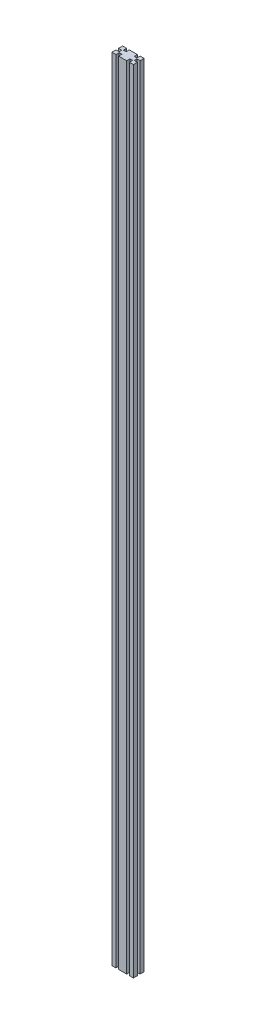
SolidWorks part; units mm, degrees
ref_plane "Front Plane" through (0, 0, 0) normal (0, 0, 1) x (1, 0, 0)
ref_plane "Top Plane" through (0, 0, 0) normal (0, 1, 0) x (1, 0, 0)
ref_plane "Right Plane" through (0, 0, 0) normal (1, 0, 0) x (0, 0, -1)
sketch "Sketch1" plane through (0, 0, 0) normal (0, 1, 0) x (1, 0, 0)
  line L1 (-20, -10) -> (20, -10)
  line L2 (-20, -10) -> (-20, 10)
  line L3 (-20, 10) -> (20, 10)
  line L4 (20, -10) -> (20, 10)
  line L5 (-20, -10) -> (20, 10) construction
  line L6 (-20, 10) -> (20, -10) construction
  point P0 (0, 0)
  dimension "D1" = 20
  dimension "D2" = 40
extrude "Boss-Extrude1" add sketch "Sketch1" along normal blind 736.6 and the other way blind 736.6
sketch "Sketch2" plane through (0, 0, 0) normal (0, 1, 0) x (1, 0, 0)
  line L0 (-20, 10) -> (0, 10) construction
  line L1 (20, 10) -> (-20, 10) construction
  line L2 (0, 10) -> (20, 10) construction
  line L4 (-20, 10) -> (-20, -10) construction
  line L5 (-12.5, 4) -> (-7.5, 4)
  line L6 (-12.5, 4) -> (-12.5, 16)
  line L7 (-12.5, 16) -> (-7.5, 16)
  line L8 (-7.5, 4) -> (-7.5, 16)
  line L9 (-12.5, 4) -> (-7.5, 16) construction
  line L10 (-12.5, 16) -> (-7.5, 4) construction
  line L11 (-14, 2.5) -> (-26, 2.5)
  line L12 (-14, 2.5) -> (-14, -2.5)
  line L13 (-14, -2.5) -> (-26, -2.5)
  line L14 (-26, 2.5) -> (-26, -2.5)
  line L15 (-14, 2.5) -> (-26, -2.5) construction
  line L16 (-14, -2.5) -> (-26, 2.5) construction
  line L17 (-55, 0) -> (55, 0) construction
  line L18 (-14, 2.5) -> (-26, -2.5) construction
  line L19 (-14, -2.5) -> (-26, 2.5) construction
  line L20 (-12.5, -16) -> (-7.5, -4) construction
  line L21 (-12.5, -4) -> (-7.5, -16) construction
  line L22 (-14, 2.5) -> (-26, 2.5)
  line L23 (-14, -2.5) -> (-26, -2.5)
  line L24 (-7.5, -4) -> (-7.5, -16)
  line L25 (-12.5, -16) -> (-7.5, -16)
  line L26 (-12.5, -4) -> (-12.5, -16)
  line L27 (-12.5, -4) -> (-7.5, -4)
  line L28 (0, -55) -> (0, 55) construction
  line L29 (12.5, -4) -> (7.5, -16) construction
  line L30 (12.5, -16) -> (7.5, -4) construction
  line L31 (14, -2.5) -> (26, 2.5) construction
  line L32 (14, 2.5) -> (26, -2.5) construction
  line L33 (14, -2.5) -> (26, 2.5) construction
  line L34 (14, 2.5) -> (26, -2.5) construction
  line L35 (12.5, 16) -> (7.5, 4) construction
  line L36 (12.5, 4) -> (7.5, 16) construction
  line L37 (20, 10) -> (0, 10) construction
  line L38 (12.5, -4) -> (7.5, -4)
  line L39 (12.5, -4) -> (12.5, -16)
  line L40 (12.5, -16) -> (7.5, -16)
  line L41 (7.5, -4) -> (7.5, -16)
  line L42 (14, -2.5) -> (26, -2.5)
  line L43 (14, 2.5) -> (26, 2.5)
  line L44 (26, 2.5) -> (26, -2.5)
  line L45 (14, -2.5) -> (26, -2.5)
  line L46 (14, 2.5) -> (14, -2.5)
  line L47 (14, 2.5) -> (26, 2.5)
  line L48 (7.5, 4) -> (7.5, 16)
  line L49 (12.5, 16) -> (7.5, 16)
  line L50 (12.5, 4) -> (12.5, 16)
  line L51 (12.5, 4) -> (7.5, 4)
  point P7 (-10, 10)
  point P12 (-20, 0)
  point P25 (-10, -10)
  point P40 (10, -10)
  point P41 (20, 0)
  point P42 (10, 10)
  dimension "D1" = 12
  dimension "D2" = 5
  dimension "D3" = 5
  dimension "D4" = 12
extrude "Cut-Extrude1" cut sketch "Sketch2" against normal through all both and the other way through all contours L5 L8 L7 L6 | L27 L26 L25 L24 | L11 L14 L13 L12 | L51 L50 L49 L48 | L43 L46 L42 L44 | L38 L41 L40 L39 region at (-10, 0, -10) region at (-20, 0, 0) region at (-10, 0, 10) region at (10, 0, 10) region at (20, 0, 0) region at (10, 0, -10)
